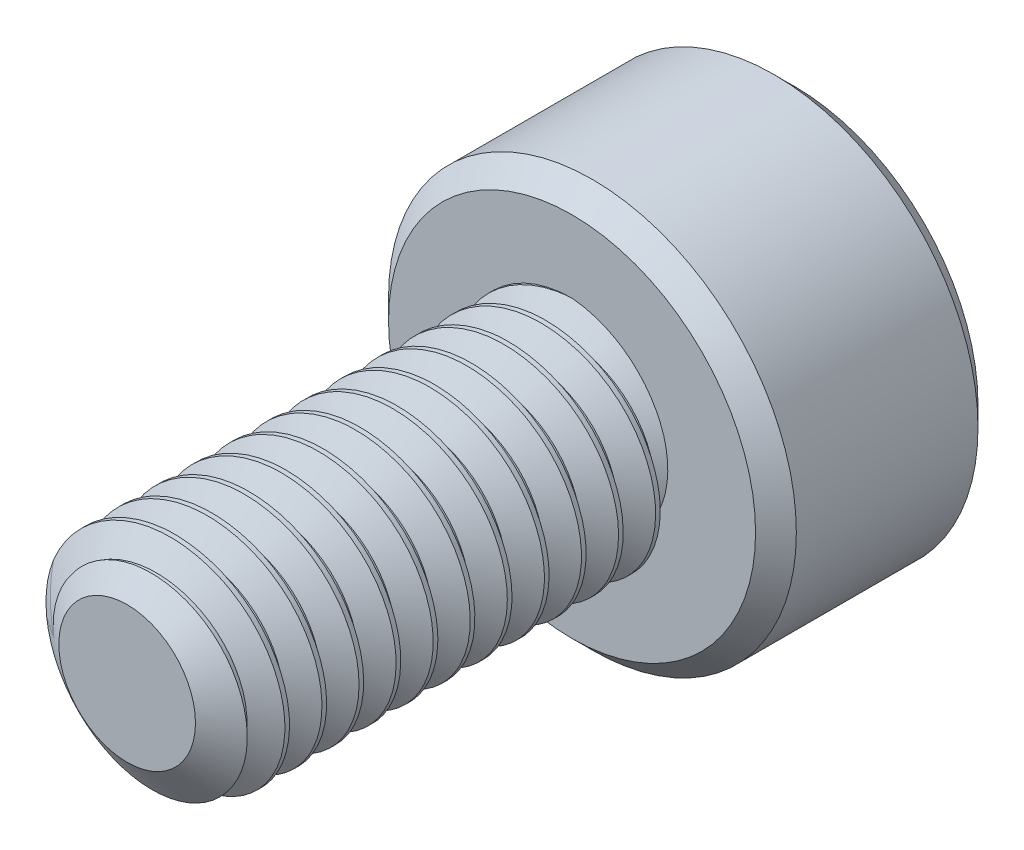
SolidWorks part; units mm, degrees
ref_plane "Front Plane" through (0, 0, 0) normal (0, 0, 1) x (1, 0, 0)
ref_plane "Top Plane" through (0, 0, 0) normal (0, 1, 0) x (1, 0, 0)
ref_plane "Right Plane" through (0, 0, 0) normal (1, 0, 0) x (0, 0, -1)
sketch "Sketch1" plane through (0, 0, 0) normal (0, 0, 1) x (1, 0, 0)
  circle A0 centre (0, 0) radius 1.5
  dimension "OD" = 3
extrude "Extrude1" add sketch "Sketch1" against normal blind 6
sketch "Sketch2" plane through (0, 0, 0) normal (0, 0, 1) x (1, 0, 0)
  circle A0 centre (0, 0) radius 1.5 construction
  circle A1 centre (0, 0) radius 1.5
curve "Helix/Spiral1" pitch 0.5 height 6.5 radius 1.5 centre (0, 0, 0) axis (0, 0, -1) start towards (0, 1, 0) parameters "pitch"=0.5
sketch "Sketch3" plane through (0, 0, 0) normal (1, 0, 0) x (0, 0, -1)
  line L0 (-0.4375, 1.5) -> (-0.25, 1.1752)
  line L1 (-0.25, 1.1752) -> (-0.1875, 1.1752)
  line L2 (-0.1875, 1.1752) -> (0, 1.5)
  line L3 (-0.4375, 1.5) -> (0, 1.5)
  line L4 (-0.2187, 1.5) -> (-0.2187, 1.1752) construction
  line L5 (-0.3438, 1.3376) -> (-0.0937, 1.3376) construction
  line L6 (0, 1.5) -> (0, -1.5) construction
  dimension "D1" = 0.0625
  dimension "D2" = 0.25
  dimension "D3" = 60
sweep "Cut-Sweep1" cut profiles "Sketch3" path "Helix/Spiral1"
sketch "Sketch4" plane through (0, 0, 0) normal (1, 0, 0) x (0, 0, -1)
  line L0 (0.4053, 1.5) -> (0, 0.9212)
  line L1 (0, 0.9212) -> (0, 1.5)
  line L2 (0.4053, 1.5) -> (0, 1.5)
  line L3 (-0.4375, 1.5) -> (0, 1.5) construction
  line L4 (0, 0) -> (7.0209, 0) construction
  dimension "D1" = 55
  dimension "D2" = 0.254
revolve "Cut-Revolve1" cut sketch "Sketch4" angle 360 about L4
sketch "Sketch6" plane through (0, 0, -6) normal (0, 0, -1) x (-1, 0, 0)
  circle A0 centre (0, 0) radius 2.75
  dimension "head dia" = 5.5
extrude "Extrude2" add sketch "Sketch6" along normal blind 3
sketch "Sketch7" plane through (0, 0, -9) normal (0, 0, -1) x (-1, 0, 0)
  line L1 (0, 1.4434) -> (-1.25, 0.7217)
  line L2 (-1.25, 0.7217) -> (-1.25, -0.7217)
  line L3 (-1.25, -0.7217) -> (0, -1.4434)
  line L4 (0, -1.4434) -> (1.25, -0.7217)
  line L5 (1.25, -0.7217) -> (1.25, 0.7217)
  line L6 (1.25, 0.7217) -> (0, 1.4434)
  circle A0 centre (0, 0) radius 1.25 construction
  dimension "hex dia" = 2.5
extrude "Cut-Extrude1" cut sketch "Sketch7" against normal blind 1.875
sketch "Sketch8" plane through (0, 0, -9) normal (0, 0, -1) x (-1, 0, 0)
  circle A0 centre (0, 0) radius 1.4434
extrude "Cut-Extrude2" cut sketch "Sketch8" against normal through all draft 45
chamfer "Chamfer1" distance 0.275 angle 45 2 edges at (-2.75, 0, -9) (-2.75, 0, -6)
sketch "Sketch9" plane through (0, 0, 0) normal (1, 0, 0) x (0, 0, -1)
  line L0 (0, 1.5) -> (0, -1.5) construction
  line L1 (2.75, 1.5) -> (2.75, -1.5) construction
  dimension "D1" = 2.75
equation "\"D3@Helix/Spiral1\" = \"screw length@Extrude1\"+\"pitch@Helix/Spiral1\""
equation "\"D1@Sketch3\" = \"pitch@Helix/Spiral1\"*.125"
equation "\"D2@Sketch3\" = \"pitch@Helix/Spiral1\"*.5"
equation "\"D1@Cut-Extrude1\" = \"hex dia@Sketch7\"*.75"
equation "\"D1@Chamfer1\" = \"head dia@Sketch6\"*.05"
equation "\"D1@Sketch9\" = \"pitch@Helix/Spiral1\"*5.5"
